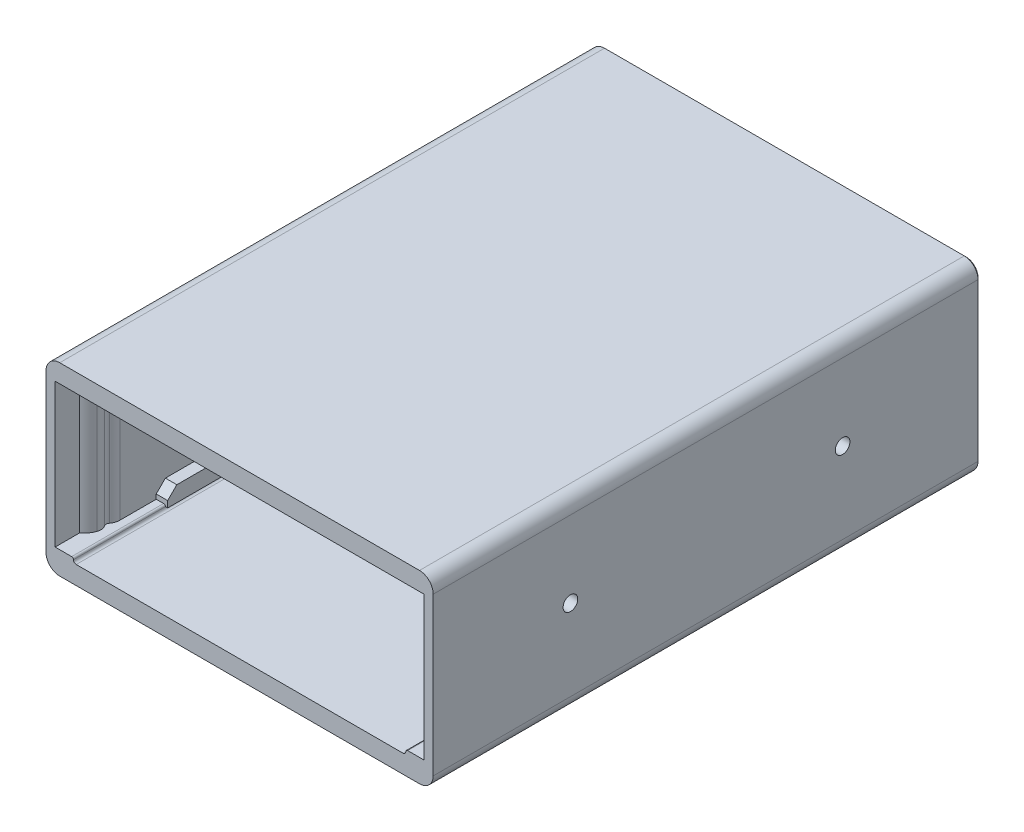
SolidWorks part; units mm, degrees
note: The reader was unsure of these and kept them because the rebuilt part matched: shared geometry of "草图3<3>", "草图3<4>".
ref_plane "Front Plane" through (0, 0, 0) normal (0, 0, 1) x (1, 0, 0)
ref_plane "Top Plane" through (0, 0, 0) normal (0, 1, 0) x (1, 0, 0)
ref_plane "Right Plane" through (0, 0, 0) normal (1, 0, 0) x (0, 0, -1)
other "Configuration Table"
sketch "草图1" plane through (0, 0, 0) normal (0, 0, 1) x (1, 0, 0)
  line L1 (-38.7561, 20.6544) -> (39.8939, 20.6544)
  line L2 (-41.7561, 17.6544) -> (-41.7561, -16.7456)
  line L3 (-38.7561, -19.7456) -> (39.8939, -19.7456)
  line L4 (42.8939, 17.6544) -> (42.8939, -16.7456)
  arc A0 (-41.7561, 17.6544) -> (-38.7561, 20.6544) centre (-38.7561, 17.6544) cw
  arc A1 (-41.7561, -16.7456) -> (-38.7561, -19.7456) centre (-38.7561, -16.7456) ccw
  arc A2 (39.8939, -19.7456) -> (42.8939, -16.7456) centre (39.8939, -16.7456) ccw
  arc A3 (42.8939, 17.6544) -> (39.8939, 20.6544) centre (39.8939, 17.6544) ccw
  point P6 (-41.7561, 20.6544)
  point P11 (42.8939, -19.7456)
  point P14 (42.8939, 20.6544)
  dimension "D3" = 3
  dimension "D1" = 84.65
  dimension "D2" = 40.4
extrude "凸台-拉伸1" add sketch "草图1" along normal blind 119.5
sketch "草图2" plane through (0, 0, 119.5) normal (0, 0, 1) x (1, 0, 0)
  line L0 (-41.7561, 17.6544) -> (-41.7561, -16.7456) construction
  line L1 (-37.7561, 16.6544) -> (38.8939, 16.6544)
  line L2 (-37.7561, 16.6544) -> (-37.7561, -14.7456)
  line L3 (-35.1561, -15.7456) -> (36.2939, -15.7456)
  line L4 (38.8939, 16.6544) -> (38.8939, -14.7456)
  line L5 (39.8939, 20.6544) -> (-38.7561, 20.6544) construction
  line L6 (38.8939, -14.7456) -> (37.3198, -14.7456)
  line L8 (-37.7561, -14.7456) -> (-36.147, -14.7456)
  line L9 (-35.7561, -15.1422) -> (-35.7561, -15.1456)
  line L10 (-38.7561, -19.7456) -> (39.8939, -19.7456) construction
  arc A0 (-35.7561, -15.1456) -> (-35.1561, -15.7456) centre (-35.1561, -15.1456) ccw
  arc A1 (36.2939, -15.7456) -> (36.8937, -15.1609) centre (36.2939, -15.1456) ccw
  arc A2 (-35.7561, -15.1422) -> (-36.147, -14.7456) centre (-36.147, -15.1365) ccw
  arc A3 (37.3198, -14.7456) -> (36.8937, -15.1609) centre (37.3198, -15.1718) ccw
  point P16 (-35.7561, -15.7456)
  point P19 (36.8939, -15.7456)
  dimension "D9" = 0.6
  dimension "D10" = 0.7819
  dimension "D11" = 0.8525
  dimension "D5" = 1.6091
  dimension "D6" = 0.609
  dimension "D7" = 1.5741
  dimension "D8" = 0.5737
  dimension "D1" = 76.65
  dimension "D2" = 4
  dimension "D3" = 4
  dimension "D4" = 4
extrude "切除-拉伸1" cut sketch "草图2" against normal blind 115.5
sketch "草图3" plane through (0, 0, 4) normal (0, 0, 1) x (1, 0, 0)
  line L1 (-28.2561, 16.6544) -> (29.3939, 16.6544)
  line L3 (-28.2561, -15.7456) -> (29.3939, -15.7456)
  line L5 (-41.7561, 17.6544) -> (-41.7561, -16.7456) construction
  line L6 (-35.1561, -15.7456) -> (36.2939, -15.7456) construction
  line L7 (38.8939, 16.6544) -> (-37.7561, 16.6544) construction
  line L8 (39.8939, 20.6544) -> (-38.7561, 20.6544) construction
  line L10 (42.8939, -16.7456) -> (42.8939, 17.6544) construction
  line L11 (-28.2561, 12.4544) -> (-28.2561, 16.6544)
  line L15 (-38.7561, -19.7456) -> (39.8939, -19.7456) construction
  line L18 (-31.7561, 8.9544) -> (-37.7561, 8.9544)
  line L19 (-37.7561, 8.9544) -> (-37.7561, -7.0456)
  line L20 (-37.7561, -7.0456) -> (-31.7561, -7.0456)
  line L21 (-28.2561, -10.5456) -> (-28.2561, -15.7456)
  line L22 (29.3939, -10.5456) -> (29.3939, -15.7456)
  line L23 (32.8939, -7.0456) -> (38.8939, -7.0456)
  line L24 (38.8939, -7.0456) -> (38.8939, 8.9544)
  line L25 (38.8939, 8.9544) -> (32.8939, 8.9544)
  line L26 (29.3939, 12.4544) -> (29.3939, 16.6544)
  line L27 (38.8939, -14.7456) -> (38.8939, 16.6544) construction
  line L28 (-37.7561, 16.6544) -> (-37.7561, -14.7456) construction
  circle A0 centre (-31.7561, -10.5456) radius 1.4
  circle A8 centre (32.8939, 12.4544) radius 1.4
  circle A10 centre (32.8939, -10.5456) radius 1.4
  circle A12 centre (-31.7561, 12.4544) radius 1.4
  arc A15 (-31.7561, 8.9544) -> (-28.2561, 12.4544) centre (-31.7561, 12.4544) ccw
  arc A16 (-28.2561, -10.5456) -> (-31.7561, -7.0456) centre (-31.7561, -10.5456) ccw
  arc A17 (32.8939, -7.0456) -> (29.3939, -10.5456) centre (32.8939, -10.5456) ccw
  arc A18 (29.3939, 12.4544) -> (32.8939, 8.9544) centre (32.8939, 12.4544) ccw
  dimension "D3" = 10
  dimension "D4" = 8.2
  dimension "D5" = 9.2
  dimension "D6" = 7
  dimension "D10" = 10
  dimension "D11" = 10
  dimension "D15" = 9.2
  dimension "D16" = 8.2
  dimension "D1" = 2.8
  dimension "D2" = 10
extrude "切除-拉伸2" cut sketch "草图3" against normal blind 4
sketch "草图4" plane through (38.8939, 0, 0) normal (-1, 0, 0) x (0, 0, 1)
  line L4 (19.4, 3.2544) -> (97.4, 3.2544)
  line L5 (19.4, 3.2544) -> (19.4, -1.3456)
  line L6 (19.4, -1.3456) -> (97.4, -1.3456)
  line L7 (99.4, 1.2544) -> (99.4, 0.6544)
  line L10 (4, 16.6544) -> (119.5, 16.6544) construction
  line L14 (119.5, 17.6544) -> (119.5, -16.7456) construction
  line L15 (99.4, 1.2544) -> (97.4, 3.2544)
  line L16 (99.4, 0.6544) -> (97.4, -1.3456)
  line L17 (4, -15.7456) -> (119.5, -15.7456) construction
  line L18 (20.1463, 16.6544) -> (99.4, 16.6544)
  line L19 (20.1463, 16.6544) -> (20.1463, 13.6544)
  line L20 (20.1463, 13.6544) -> (97.4, 13.6544)
  line L21 (99.4, 16.6544) -> (99.4, 15.6544)
  line L22 (19.4, -11.7456) -> (97.4, -11.7456)
  line L23 (19.4, -11.7456) -> (19.4, -15.1456)
  line L24 (19.4, -15.1456) -> (99.4, -15.1456)
  line L25 (99.4, -13.7456) -> (99.4, -15.1456)
  line L27 (99.4, 15.6544) -> (97.4, 13.6544)
  line L28 (99.4, -13.7456) -> (97.4, -11.7456)
  dimension "D1" = 20.1
  dimension "D2" = 4.6
  dimension "D3" = 13.4
  dimension "D4" = 80
  dimension "D5" = 0.6
  dimension "D6" = 2
  dimension "D7" = 2
  dimension "D8" = 2
  dimension "D9" = 1
  dimension "D10" = 80
  dimension "D11" = 2
  dimension "D12" = 20.1
  dimension "D13" = 20.1
  dimension "D14" = 3
  dimension "D15" = 4
  dimension "D16" = 2
  dimension "D17" = 2
  dimension "D18" = 3.4
extrude "凸台-拉伸2" add sketch "草图4" along normal blind 2.5
sketch "草图6" plane through (-37.7561, 0, 0) normal (1, 0, 0) x (0, 0, -1)
  line L0 (-119.5, -16.7456) -> (-119.5, 17.6544) construction
  line L1 (-99.4, 16.6544) -> (-19.4, 16.6544)
  line L2 (-99.4, 16.6544) -> (-99.4, 15.6544)
  line L3 (-97.4, 13.6544) -> (-19.4, 13.6544)
  line L4 (-19.4, 16.6544) -> (-19.4, 13.6544)
  line L5 (-97.4, 3.2544) -> (-19.4, 3.2544)
  line L6 (-99.4, 1.2544) -> (-99.4, 0.6544)
  line L7 (-97.4, -1.3456) -> (-19.4, -1.3456)
  line L8 (-19.4, 3.2544) -> (-19.4, -1.3456)
  line L9 (-97.4, -11.7456) -> (-19.4, -11.7456)
  line L10 (-99.4, -13.7456) -> (-99.4, -15.1456)
  line L11 (-99.4, -15.1456) -> (-19.4, -15.1456)
  line L12 (-19.4, -11.7456) -> (-19.4, -15.1456)
  line L13 (-99.4, 15.6544) -> (-97.4, 13.6544)
  line L14 (-99.4, 1.2544) -> (-97.4, 3.2544)
  line L15 (-99.4, 0.6544) -> (-97.4, -1.3456)
  line L16 (-99.4, -13.7456) -> (-97.4, -11.7456)
  line L17 (-4, 16.6544) -> (-119.5, 16.6544) construction
  line L18 (-4, -15.7456) -> (-119.5, -15.7456) construction
  dimension "D1" = 20.1
  dimension "D2" = 20.1
  dimension "D3" = 20.1
  dimension "D4" = 80
  dimension "D5" = 80
  dimension "D6" = 80
  dimension "D7" = 4.6
  dimension "D8" = 3
  dimension "D9" = 3.4
  dimension "D10" = 0.6
  dimension "D11" = 2
  dimension "D12" = 2
  dimension "D13" = 2
  dimension "D14" = 13.4
  dimension "D15" = 1
  dimension "D16" = 2
  dimension "D17" = 2
  dimension "D18" = 2
  dimension "D19" = 4
extrude "凸台-拉伸3" add sketch "草图6" along normal blind 2.5
sketch "草图8" plane through (0, 16.6544, 0) normal (0, -1, 0) x (1, 0, 0)
  line L0 (-39.7561, 114.19) -> (-39.7561, 119.5)
  line L1 (-38.7561, 119.5) -> (39.8939, 119.5) construction
  line L2 (-39.7561, 119.5) -> (-34.7561, 119.5)
  line L6 (-34.7561, 119.5) -> (-34.7561, 107.3053)
  line L8 (-41.7561, 119.5) -> (-41.7561, 0) construction
  line L9 (-37.7561, 107.3053) -> (-34.7561, 107.3053)
  line L10 (42.8939, 119.5) -> (42.8939, 0) construction
  line L12 (38.8939, 107.1805) -> (35.8939, 107.1805)
  line L13 (35.8939, 119.5) -> (35.8939, 107.1805)
  line L14 (40.8939, 119.5) -> (35.8939, 119.5)
  line L15 (40.8939, 114.19) -> (40.8939, 119.5)
  arc A0 (-39.7561, 114.19) -> (-38.1261, 111.93) centre (-42.8358, 110.251) cw
  arc A2 (-38.1261, 111.93) -> (-38.3463, 110.1483) centre (-40.01, 111.2584) cw
  arc A3 (-38.3463, 110.1483) -> (-38.3257, 109.0641) centre (-37.5561, 109.621) ccw
  arc A4 (-38.3257, 109.0641) -> (-37.7561, 107.3053) centre (-40.7561, 107.3053) cw
  arc A5 (39.4635, 108.9393) -> (38.8939, 107.1805) centre (41.8939, 107.1805) ccw
  arc A6 (39.4618, 110.0555) -> (39.4635, 108.9393) centre (38.6939, 109.4962) cw
  arc A7 (39.2039, 111.93) -> (39.4618, 110.0555) centre (41.0785, 111.233) ccw
  arc A8 (40.8939, 114.19) -> (39.2039, 111.93) centre (43.8904, 110.1874) ccw
  dimension "D1" = 5
  dimension "D2" = 2
  dimension "D3" = 0.95
  dimension "D4" = 3
  dimension "D9" = 4.2
  dimension "D14" = 5
  dimension "D15" = 2
  dimension "D16" = 0.95
  dimension "D17" = 3
  dimension "D22" = 4.2
  dimension "D5" = 5.31
  dimension "D6" = 7.57
  dimension "D7" = 3.63
  dimension "D8" = 2
  dimension "D10" = 4
  dimension "D11" = 5
  dimension "D12" = 5
  dimension "D13" = 5.31
  dimension "D18" = 4
  dimension "D19" = 2
  dimension "D20" = 3.69
  dimension "D21" = 7.57
extrude "切除-拉伸3" cut sketch "草图8" along normal blind 31.4
chamfer "倒角1" distance 0.4 angle 45 8 edges at (-40.8774, 19.7758, 0) (-41.7561, 0.4544, 0) (-40.8774, -18.8669, 0) (0.5689, -19.7456, 0) (42.0152, -18.8669, 0) (42.8939, 0.4544, 0) (42.0152, 19.7758, 0) (0.5689, 20.6544, 0)
extrude "切除-拉伸4" cut sketch "草图3<3>" against normal blind 2.5
sketch "草图3<3>" plane through (0, 0, 4) normal (0, 0, 1) x (1, 0, 0) same geometry as "草图3"
extrude "切除-拉伸5" cut sketch "草图3<4>" against normal blind 4
sketch "草图3<4>" plane through (0, 0, 4) normal (0, 0, 1) x (1, 0, 0) same geometry as "草图3"
sketch "草图9" plane through (42.8939, 0, 0) normal (1, 0, 0) x (0, 0, -1)
  line L0 (-119.5, -16.7456) -> (-119.5, 17.6544) construction
  line L1 (0, 17.6544) -> (0, -16.7456) construction
  line L2 (-119.5, 20.6544) -> (-0.4, 20.6544) construction
  circle A0 centre (-89.5, 0.9544) radius 1.6
  circle A1 centre (-30, 0.9544) radius 1.6
  dimension "D1" = 3.2
  dimension "D2" = 30
  dimension "D3" = 30
  dimension "D4" = 19.7
  dimension "D5" = 19.7
extrude "切除-拉伸6" cut sketch "草图9" against normal through all
chamfer "倒角4" distance 0.4 angle 45 20 edges at (34.2939, 12.4544, 0) (34.2939, -10.5456, 0) (-30.3561, -10.5456, 0) (0.5689, 16.6544, 0) (29.3939, 14.5544, 0) (30.419, 9.9796, 0) (35.8939, 8.9544, 0) (38.8939, 0.9544, 0) (35.8939, -7.0456, 0) (30.419, -8.0707, 0) (29.3939, -13.1456, 0) (0.5689, -15.7456, 0) (-28.2561, -13.1456, 0) (-29.2812, -8.0707, 0) (-34.7561, -7.0456, 0) (-37.7561, 0.9544, 0) (-34.7561, 8.9544, 0) (-29.2812, 9.9796, 0) (-28.2561, 14.5544, 0) (-30.3561, 12.4544, 0)
chamfer "倒角5" distance 0.4 angle 45 16 edges at (29.3939, -13.1456, 4) (30.419, -8.0707, 4) (35.8939, -7.0456, 4) (34.2939, -10.5456, 4) (34.2939, 12.4544, 4) (29.3939, 14.5544, 4) (30.419, 9.9796, 4) (35.8939, 8.9544, 4) (-30.3561, -10.5456, 4) (-28.2561, -13.1456, 4) (-34.7561, -7.0456, 4) (-29.2812, -8.0707, 4) (-34.7561, 8.9544, 4) (-29.2812, 9.9796, 4) (-28.2561, 14.5544, 4) (-30.3561, 12.4544, 4)
